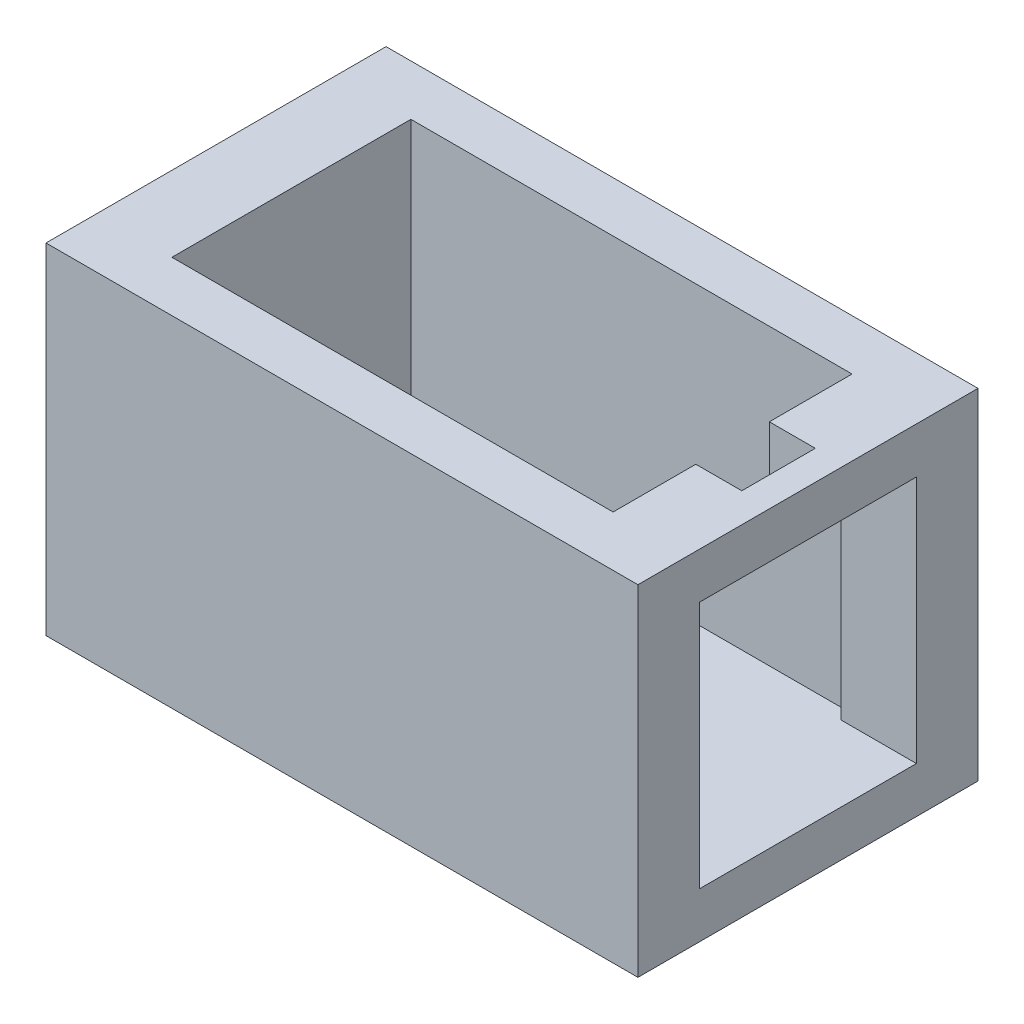
SolidWorks part; units mm, degrees
ref_plane "Front Plane" through (0, 0, 0) normal (0, 0, 1) x (1, 0, 0)
ref_plane "Top Plane" through (0, 0, 0) normal (0, 1, 0) x (1, 0, 0)
ref_plane "Right Plane" through (0, 0, 0) normal (1, 0, 0) x (0, 0, -1)
sketch "Sketch2" plane through (0, 0, 0) normal (0, 1, 0) x (1, 0, 0)
  line L1 (16.1, -9.25) -> (-16.1, -9.25)
  line L2 (16.1, -9.25) -> (16.1, 9.25)
  line L3 (16.1, 9.25) -> (-16.1, 9.25)
  line L4 (-16.1, -9.25) -> (-16.1, 9.25)
  line L5 (16.1, -9.25) -> (-16.1, 9.25) construction
  line L6 (16.1, 9.25) -> (-16.1, -9.25) construction
  point P0 (0, 0)
  dimension "D1" = 18.5
  dimension "D2" = 32.2
extrude "Boss-Extrude1" add sketch "Sketch2" against normal blind 18.5 contours L1 L4 L3 L2
sketch "Sketch3" plane through (0, 0, 0) normal (0, 1, 0) x (1, 0, 0)
  line L1 (12, -6.5) -> (-12, -6.5)
  line L2 (12, -6.5) -> (12, 6.5)
  line L3 (12, 6.5) -> (-12, 6.5)
  line L4 (-12, -6.5) -> (-12, 6.5)
  line L5 (12, -6.5) -> (-12, 6.5) construction
  line L6 (12, 6.5) -> (-12, -6.5) construction
  point P0 (0, 0)
  dimension "D1" = 13
  dimension "D2" = 24
extrude "Cut-Extrude1" cut sketch "Sketch3" against normal blind 16 contours L3 L4 L1 L2
sketch "Sketch4" plane through (16.1, 0, 0) normal (1, 0, 0) x (0, 0, -1)
  line L0 (0, 0) -> (0, -18.5) construction
  line L1 (-9.25, -18.5) -> (9.25, -18.5) construction
  line L3 (5.9, -16) -> (-5.9, -16)
  line L4 (5.9, -16) -> (5.9, -2.5)
  line L5 (5.9, -2.5) -> (-5.9, -2.5)
  line L6 (-5.9, -16) -> (-5.9, -2.5)
  point P5 (0, -9.25)
  dimension "D1" = 5.9
  dimension "D2" = 6.75
  dimension "D3" = 6.75
  dimension "D4" = 11.8
extrude "Cut-Extrude2" cut sketch "Sketch4" against normal blind 5
sketch "Sketch5" plane through (0, 0, 0) normal (0, 1, 0) x (1, 0, 0)
  line L0 (12, -6.5) -> (12, 6.5) construction
  line L1 (14.5, -2) -> (12, -2)
  line L2 (14.5, -2) -> (14.5, 2)
  line L3 (14.5, 2) -> (12, 2)
  line L7 (12, 2) -> (12, -2)
  point P0 (12, 0)
  dimension "D1" = 4
  dimension "D2" = 2
  dimension "D3" = 2.5
  dimension "D4" = 2.5
extrude "Cut-Extrude3" cut sketch "Sketch5" against normal blind 2.5
sketch "Sketch7" plane through (0, -18.5, 0) normal (0, -1, 0) x (1, 0, 0)
  line L2 (16.1, -9.25) -> (-16.1, -9.25) construction
  line L3 (12, 6.5) -> (12, 2) construction
  circle A0 centre (6.1, -0.85) radius 3.5
  dimension "D1" = 7
  dimension "D2" = 5.9
  dimension "D3" = 8.4
extrude "Boss-Extrude2" add sketch "Sketch7" along normal blind 5 contours A0
